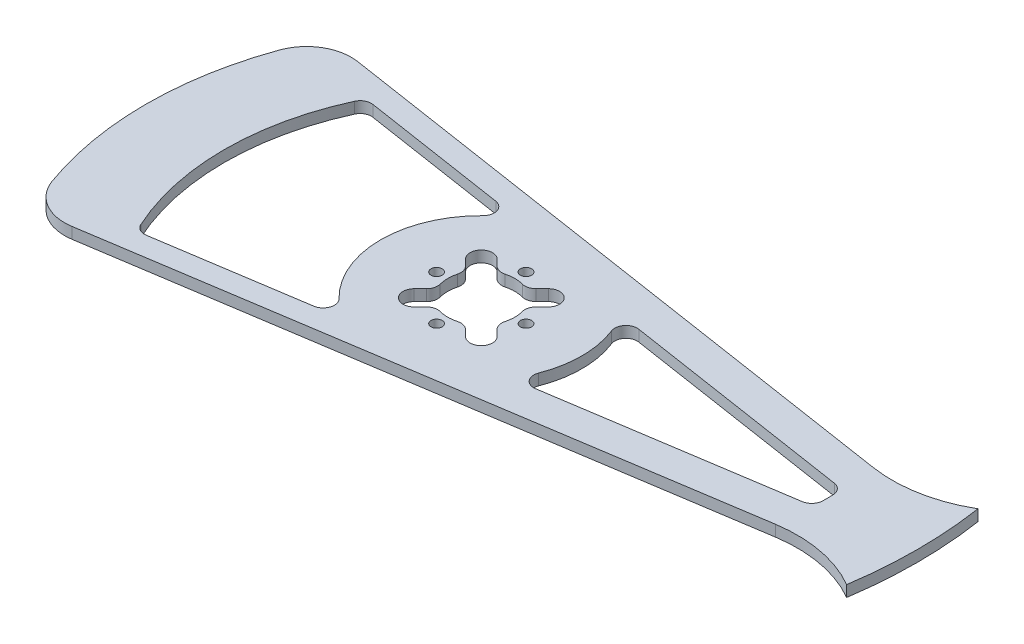
SolidWorks part; units mm, degrees
material "AISI 4340 Steel, normalized"
ref_plane "Front Plane" through (0, 0, 0) normal (0, 0, 1) x (1, 0, 0)
ref_plane "Top Plane" through (0, 0, 0) normal (0, 1, 0) x (1, 0, 0)
ref_plane "Right Plane" through (0, 0, 0) normal (1, 0, 0) x (0, 0, -1)
other "Center of Mass"
sketch "Sketch1" plane through (0, 0, 0) normal (0, 1, 0) x (1, 0, 0)
  line L0 (-170.9166, 84.1295) -> (194.8729, 27.8292)
  line L1 (-170.9166, -84.1295) -> (194.8729, -27.8292)
  line L2 (-130.6087, 65.076) -> (-28.7411, 49.3971)
  line L3 (-130.6087, -65.076) -> (-28.7411, -49.3971)
  line L4 (47.8972, 31.1766) -> (196.6759, 8.2773)
  line L5 (47.8972, -31.1766) -> (196.6759, -8.2773)
  line L6 (-23.5401, 14.5599) -> (-17.1901, 8.2099)
  line L7 (-19.05, -19.05) -> (19.05, -19.05) construction
  line L8 (-19.05, -19.05) -> (-19.05, 19.05) construction
  line L9 (-19.05, 19.05) -> (19.05, 19.05) construction
  line L10 (19.05, -19.05) -> (19.05, 19.05) construction
  line L11 (-19.05, -19.05) -> (19.05, 19.05) construction
  line L12 (-19.05, 19.05) -> (19.05, -19.05) construction
  line L13 (-14.5599, 23.5401) -> (-8.2099, 17.1901)
  line L14 (23.5401, 14.5599) -> (17.1901, 8.2099)
  line L15 (14.5599, 23.5401) -> (8.2099, 17.1901)
  line L16 (14.5599, -23.5401) -> (8.2099, -17.1901)
  line L17 (23.5401, -14.5599) -> (17.1901, -8.2099)
  line L18 (-23.5401, -14.5599) -> (-17.1901, -8.2099)
  line L19 (-14.5599, -23.5401) -> (-8.2099, -17.1901)
  line L20 (0, 0) -> (244.8246, 37.3019) construction
  circle A0 centre (0, 0) radius 57.15 construction
  circle A1 centre (0, 0) radius 247.65 construction
  arc A2 (244.8246, 37.3019) -> (244.8246, -37.3019) centre (0, 0) cw
  arc A3 (194.8729, -27.8292) -> (244.8246, -37.3019) centre (206.4647, -103.1423) cw
  arc A4 (194.8729, 27.8292) -> (244.8246, 37.3019) centre (206.4647, 103.1423) ccw
  circle A5 centre (0, 0) radius 190.5 construction
  arc A6 (-170.9166, 84.1295) -> (-170.9166, -84.1295) centre (0, 0) ccw
  circle A7 centre (0, 0) radius 196.85 construction
  circle A8 centre (0, 0) radius 145.923 construction
  arc A9 (-130.6087, 65.076) -> (-130.6087, -65.076) centre (0, 0) ccw
  arc A10 (-28.7411, 49.3971) -> (-28.7411, -49.3971) centre (0, 0) ccw
  arc A11 (47.8972, 31.1766) -> (47.8972, -31.1766) centre (0, 0) cw
  arc A12 (196.6759, 8.2773) -> (196.6759, -8.2773) centre (0, 0) cw
  circle A13 centre (0, 0) radius 19.05
  circle A14 centre (-19.05, 19.05) radius 6.35
  circle A15 centre (19.05, 19.05) radius 6.35
  circle A16 centre (19.05, -19.05) radius 6.35
  circle A17 centre (-19.05, -19.05) radius 6.35
  point P18 (-190.5, 0)
  point P59 (0, 0)
  dimension "D1" = 495.3
  dimension "D2" = 50.8
  dimension "D3" = 17.5
  dimension "D4" = 114.3
  dimension "D5" = 57.15
  dimension "D6" = 76.2
  dimension "D9" = 44.577
  dimension "D12" = 38.1
  dimension "D14" = 12.7
  dimension "D15" = 4
  dimension "D7" = 12.7
  dimension "D8" = 12.7
  dimension "D10" = 19.05
  dimension "D11" = 19.05
  dimension "D13" = 38.1
extrude "Boss-Extrude1" add sketch "Sketch1" along normal blind 6.35 contours L0 A6 L1 A3 A2 A4 L2 A10 L3 A9 region at (11.2642, 0, -51.3405)
fillet "Fillet1" radius 6.35 8 edges at (47.8972, 3.175, 31.1766) (47.8972, 3.175, -31.1766) (196.6759, 3.175, -8.2773) (196.6759, 3.175, 8.2773) (-130.6087, 3.175, -65.076) (-130.6087, 3.175, 65.076) (-28.7411, 3.175, -49.3971) (-28.7411, 3.175, 49.3971)
fillet "Fillet2" radius 25.4 2 edges at (-170.9166, 3.175, -84.1295) (-170.9166, 3.175, 84.1295)
fillet "Fillet3" radius 6.35 8 edges at (-8.2099, 3.175, 17.1901) (8.2099, 3.175, 17.1901) (17.1901, 3.175, 8.2099) (17.1901, 3.175, -8.2099) (-8.2099, 3.175, -17.1901) (8.2099, 3.175, -17.1901) (-17.1901, 3.175, -8.2099) (-17.1901, 3.175, 8.2099)
sketch "Sketch2" plane through (0, 6.35, 0) normal (0, 1, 0) x (1, 0, 0)
  circle A0 centre (0, 25.4) radius 3.175
  arc A1 (4.9305, 18.4009) -> (-4.9305, 18.4009) centre (0, 0) ccw construction
  circle A2 centre (25.4, 0) radius 3.175
  circle A3 centre (0, -25.4) radius 3.175
  circle A4 centre (-25.4, 0) radius 3.175
  point P2 (0, 19.05)
  point P15 (0, 0)
  dimension "D1" = 6.35
  dimension "D2" = 6.35
  dimension "D3" = 4
extrude "Cut-Extrude1" cut sketch "Sketch2" against normal through all
